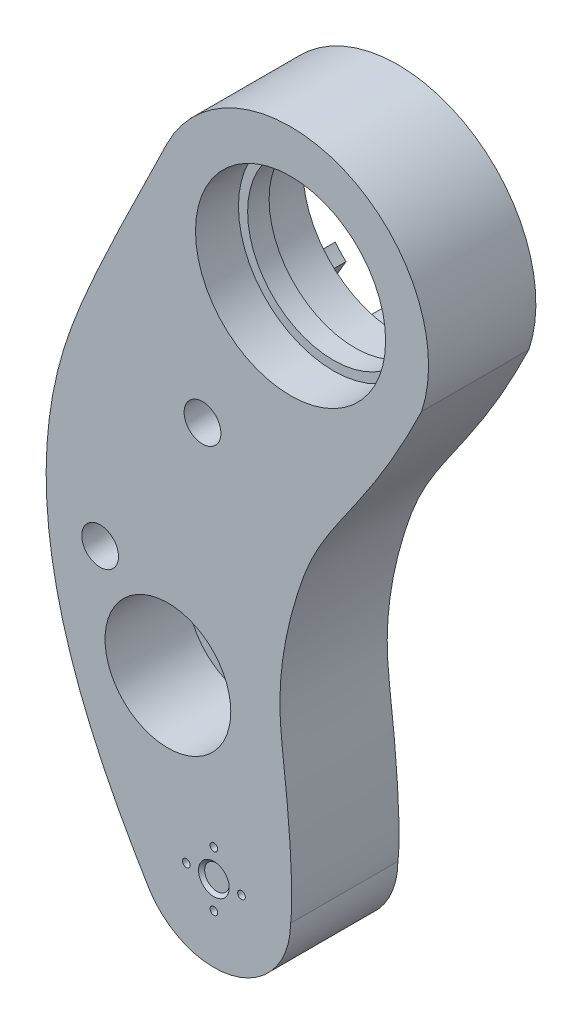
SolidWorks part; units mm, degrees
ref_plane "Ebene vorne" through (0, 0, 0) normal (0, 0, 1) x (1, 0, 0)
ref_plane "Ebene oben" through (0, 0, 0) normal (0, 1, 0) x (1, 0, 0)
ref_plane "Ebene rechts" through (0, 0, 0) normal (1, 0, 0) x (0, 0, -1)
sketch "Skizze1" plane through (0, 0, 0) normal (0, 0, 1) x (1, 0, 0)
  circle A0 centre (0, 0) radius 9
  circle A6 centre (0, 0) radius 25
  circle A7 centre (25, 180) radius 45
  circle A8 centre (25, 180) radius 28
  spline S0 degree 3 poles (-15.2208, 200.1813) (-37.2573, 155.4099) (-73.4434, 79.5174) (-38.6711, 15.7685) (-20.9233, -13.6827) knots 0 0 0 0 0.231883 1 1 1 1
  spline S1 degree 3 poles (67.7341, 165.9004) (51.1385, 131.5089) (36.2521, 119.622) (25.0061, 88.4676) (20.0361, 66.2697) (25.6637, 21.506) (25.7093, 4.904) (25, 0) knots 0 0 0 0 0.347734 0.409135 0.591244 0.652607 1 1 1 1
  point P14 (0, 0)
  dimension "D1" = 18
  dimension "D3" = 50
  dimension "D5" = 90
  dimension "D7" = 56
  dimension "D4" = 180
  dimension "D6" = 25
extrude "Aufsatz-Linear austragen1" add sketch "Skizze1" along normal blind 35 contours S1 A7 S0 | S1 A7 S0 A6 | A6 S0 A0 | A0 region at (0, 0, 0) region at (-20.8092, -12.5008, 0) region at (-11.7098, 87.9057, 0) region at (2.5666, 142.4659, 0)
sketch "Skizze2" plane through (0, 0, 35) normal (0, 0, 1) x (1, 0, 0)
  circle A0 centre (0, 0) radius 4
  dimension "D1" = 8
extrude "Schnitt-Linear austragen1" cut sketch "Skizze2" against normal blind 1 contours A0
chamfer "Fase1" distance 1 angle 45 1 edges at (4, 0, 35)
sketch "Skizze3" plane through (0, 0, 35) normal (0, 0, 1) x (1, 0, 0)
sketch "Skizze4" plane through (0, 0, 35) normal (0, 0, 1) x (1, 0, 0)
  arc A0 (-1.247, 8.9132) -> (-8.9132, 1.247) centre (0, 0) ccw
  circle A1 centre (9, 0) radius 1.25
  circle A2 centre (0, -9) radius 1.25
  circle A3 centre (-9, 0) radius 1.25
  circle A4 centre (0, 9) radius 1.25
  arc A5 (-8.9132, -1.247) -> (-1.247, -8.9132) centre (0, 0) ccw
  arc A6 (8.9132, 1.247) -> (1.247, 8.9132) centre (0, 0) ccw
  arc A7 (1.247, -8.9132) -> (8.9132, -1.247) centre (0, 0) ccw
  point P14 (0, 0)
  dimension "D1" = 18
  dimension "D2" = 4
  dimension "D3" = 2.5
extrude "Schnitt-Linear austragen2" cut sketch "Skizze4" against normal blind 15 contours A4 | A1 | A2 | A3 region at (0, 9, 35) region at (-9, 0, 35) region at (9, 0, 35) region at (0, -9, 35)
sketch "Skizze5" plane through (0, 0, 0) normal (0, 0, -1) x (-1, 0, 0)
  circle A0 centre (0, 0) radius 8
  circle A1 centre (8, 0) radius 1.25
  circle A2 centre (0, -8) radius 1.25
  circle A3 centre (-8, 0) radius 1.25
  circle A4 centre (0, 8) radius 1.25
  circle A5 centre (0, 0) radius 9.25
  point P14 (0, 0)
  dimension "D1" = 4
  dimension "D3" = 16
extrude "Schnitt-Linear austragen3" cut sketch "Skizze5" against normal blind 15 contours A0 A4 | A0 A4 | A0 A3 | A0 A3 | A0 A1 | A0 A1 | A0 A2 | A0 A2 region at (-7.4523, 0, 0) region at (-8.5125, 0, 0) region at (0, 7.4523, 0) region at (0, 8.5125, 0) region at (0, -8.5125, 0) region at (0, -7.4523, 0) region at (7.4523, 0, 0) region at (8.5125, 0, 0)
sketch "Skizze6" plane through (0, 0, 35) normal (0, 0, 1) x (1, 0, 0)
  line L0 (-49.7352, 50) -> (22.1206, 50) construction
  circle A1 centre (-15, 50) radius 12.5
  spline S0 degree 3 poles (-15.2208, 200.1813) (-37.2573, 155.4099) (-73.4434, 79.5174) (-38.6711, 15.7685) (-20.9233, -13.6827) knots 0 0 0 0 0.231883 1 1 1 1 construction
  spline S1 degree 3 poles (67.7341, 165.9004) (51.1385, 131.5089) (36.2521, 119.622) (25.0061, 88.4676) (20.0361, 66.2697) (25.6637, 21.506) (25.7093, 4.904) (25, 0) knots 0 0 0 0 0.347734 0.409135 0.591244 0.652607 1 1 1 1 construction
  dimension "D1" = 50
  dimension "D2" = 25
  dimension "D3" = 15
extrude "Schnitt-Linear austragen4" cut sketch "Skizze6" against normal blind 35
sketch "Skizze7" plane through (0, 0, 35) normal (0, 0, 1) x (1, 0, 0)
  circle A0 centre (-15, 50) radius 20.5
  dimension "D1" = 41
extrude "Schnitt-Linear austragen5" cut sketch "Skizze7" against normal offset from surface (27 mm away) 8 up to face at (-2.5, 50, 0)
sketch "Skizze8" plane through (0, 0, 8) normal (0, 0, 1) x (1, 0, 0)
  line L0 (-15, 50) -> (-13.8879, 32.5354) construction
  arc A0 (-18.0975, 67.2237) -> (-32.4775, 50.8878) centre (-15, 50) ccw
  circle A1 centre (-13.8879, 32.5354) radius 2
  circle A2 centre (-32.4646, 48.8879) radius 2
  circle A3 centre (-16.1121, 67.4646) radius 2
  circle A4 centre (2.4646, 51.1121) radius 2
  arc A5 (2.2237, 53.0975) -> (-14.1122, 67.4775) centre (-15, 50) ccw
  arc A6 (-11.9025, 32.7763) -> (2.2237, 53.0975) centre (-15, 50) ccw
  arc A7 (-32.4775, 50.8878) -> (-15.8878, 32.5225) centre (-15, 50) ccw
  point P14 (-15, 50)
  dimension "D1" = 4
  dimension "D2" = 4
  dimension "D3" = 17.5
extrude "Schnitt-Linear austragen6" cut sketch "Skizze8" against normal blind 15 contours A4 | A3 | A1 | A2 | A2 | A4 region at (-16.1121, 67.4646, 8) region at (-31.5973, 48.9431, 8) region at (1.5973, 51.0569, 8) region at (-13.8879, 32.5354, 8)
sketch "Skizze9" plane through (0, 0, 0) normal (0, 0, -1) x (-1, 0, 0)
  circle A0 centre (13.8879, 32.5354) radius 3.5
  circle A1 centre (-2.4646, 51.1121) radius 3.5
  circle A2 centre (16.1121, 67.4646) radius 3.5
  circle A3 centre (32.4646, 48.8879) radius 3.5
  point P3 (15, 50)
  point P14 (15, 50)
  dimension "D1" = 7
  dimension "D2" = 4
extrude "Schnitt-Linear austragen7" cut sketch "Skizze9" against normal blind 4
sketch "Skizze10" plane through (0, 0, 35) normal (0, 0, 1) x (1, 0, 0)
  circle A0 centre (25, 180) radius 31
  dimension "D1" = 62
extrude "Schnitt-Linear austragen8" cut sketch "Skizze10" against normal blind 14
ref_plane "Ebene1" through (0, 0, 17.5) normal (0, 0, 1) x (1, 0, 0)
mirror "Spiegeln1" about plane through (0, 0, 17.5) normal (0, 0, 1) of "Schnitt-Linear austragen8"
sketch "Skizze11" plane through (0, 0, 0) normal (0, 0, 1) x (1, 0, 0)
  circle A0 centre (12.8689, 101.3867) radius 1.65
extrude "Schnitt-Linear austragen10" cut sketch "Skizze11" along normal blind 15
sketch "Skizze12" plane through (0, 0, 0) normal (0, 0, -1) x (-1, 0, 0)
  line L1 (-2, 140) -> (-25, 180) construction
  circle A0 centre (-2, 140) radius 2.1
  circle A1 centre (-25, 180) radius 32
  circle A2 centre (-2, 140) radius 7.5
  circle A3 centre (-25, 180) radius 28 construction
  dimension "D1" = 4.2
  dimension "D2" = 15
  dimension "D3" = 64
  dimension "D4" = 40
  dimension "D5" = 23
extrude "Schnitt-Linear austragen11" cut sketch "Skizze12" against normal blind 15 contours A0 region at (2, 140, 0)
sketch "Sketch1" plane through (0, 0, 0) normal (0, 0, -1) x (-1, 0, 0)
  line L0 (-15.2142, 148.9382) -> (-8.0683, 136.5107)
  line L1 (-8.0683, 136.5107) -> (-15.5036, 149.4416) construction
  line L2 (-3.0775, 155.9168) -> (4.0522, 143.5173)
  line L3 (4.0683, 143.4893) -> (-3.3669, 156.4202) construction
  line L4 (4.0522, 143.5173) -> (0.4436, 159.6723)
  line L5 (-8.0683, 136.5107) -> (-20.8701, 147.6961)
  circle A0 centre (-25, 180) radius 32.5668
extrude "Boss-Extrude1" add sketch "Sketch1" along normal blind 5 contours A0 L5 L0 | A0 L2 L4 region at (14.6753, 144.3322, 0) region at (-0.4905, 152.988, 0)
sketch "Sketch2" plane through (0, 0, 0) normal (0, 0, -1) x (-1, 0, 0)
  circle A0 centre (3.7104, 126.9928) radius 6
extrude "Cut-Extrude1" cut sketch "Sketch2" against normal blind 35
ref_plane "Plane1" through (0, 0, 30) normal (0, 0, -1) x (-1, 0, 0)
sketch "Sketch3" plane through (0, 0, 17.5) normal (0, 0, -1) x (-1, 0, 0)
  line L0 (42.1385, 78.7616) -> (8.7446, 130.2574)
  line L1 (-1.3237, 123.7283) -> (32.0702, 72.2325)
  circle A1 centre (3.7104, 126.9928) radius 6
  circle A2 centre (37.1044, 75.4971) radius 6
extrude "Cut-Extrude2" cut sketch "Sketch3" along normal blind 8 contours A2 L0 L1 | A2 region at (-20.4074, 101.2449, 17.5) region at (-37.1044, 75.4971, 17.5)
sketch "Sketch4" plane through (0, 0, 35) normal (0, 0, 1) x (1, 0, 0)
  circle A0 centre (-37.1044, 75.4971) radius 6
  arc A1 (-42.1385, 78.7616) -> (-32.0702, 72.2325) centre (-37.1044, 75.4971) ccw construction
extrude "Cut-Extrude3" cut sketch "Sketch4" against normal blind 10
sketch "Skizze13" plane through (0, 0, 0) normal (0, 0, -1) x (-1, 0, 0)
  circle A0 centre (-56.5743, 156.9002) radius 1.65
  circle A1 centre (6.8989, 202.3928) radius 1.65
  circle A2 centre (39.5617, 32.3591) radius 1.65
  circle A3 centre (-16.0818, 52.3597) radius 1.65
extrude "Schnitt-Linear austragen12" cut sketch "Skizze13" against normal blind 15
